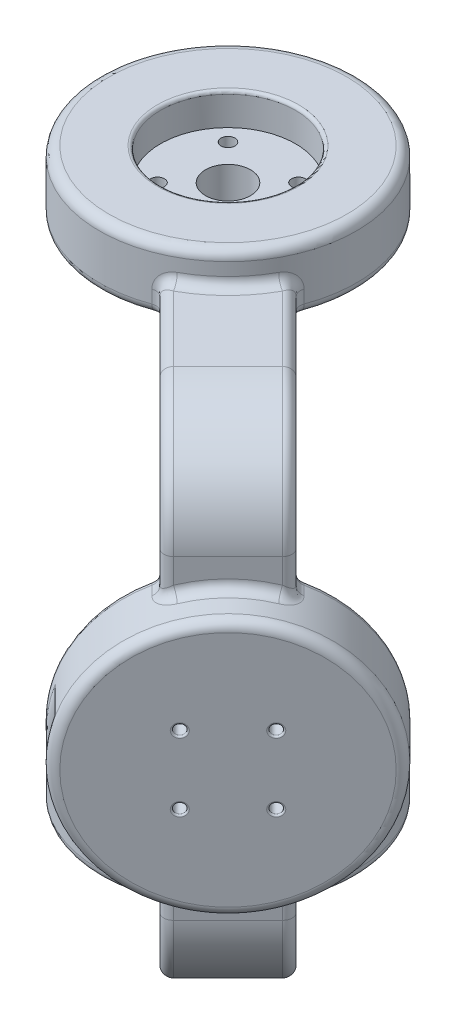
SolidWorks part; units mm, degrees
note: The reader was unsure of these and kept them because the rebuilt part matched: shared geometry of "草图6<4>".
ref_plane "前视基准面" through (0, 0, 0) normal (0, 0, 1) x (1, 0, 0)
ref_plane "上视基准面" through (0, 0, 0) normal (0, 1, 0) x (1, 0, 0)
ref_plane "右视基准面" through (0, 0, 0) normal (1, 0, 0) x (0, 0, -1)
other "Configuration Table"
sketch "草图2" plane through (0, 0, 0) normal (0, 0, 1) x (1, 0, 0)
  line L1 (30, -3) -> (30, -6)
  line L2 (30, -6) -> (40, -6)
  line L3 (40, -6) -> (40, 5)
  line L4 (25, 5) -> (0, 5)
  line L5 (0, 5) -> (0, 0)
  line L6 (0, 0) -> (25, 0)
  line L7 (25, 0) -> (25, -3)
  line L8 (25, -3) -> (30, -3)
  line L9 (40, 5) -> (40, 14)
  line L10 (40, 14) -> (25, 14)
  line L11 (25, 14) -> (25, 5)
revolve "旋转1" add sketch "草图2" angle 360 about L5
sketch "草图3" plane through (0, 0, 0) normal (0, -1, 0) x (1, 0, 0)
  circle A0 centre (12.5, 0) radius 1.6
  circle A1 centre (0, -12.5) radius 1.6
  circle A2 centre (-12.5, 0) radius 1.6
  circle A3 centre (0, 12.5) radius 1.6
  point P13 (0, 0)
  dimension "D1" = 4
extrude "切除-拉伸1" cut sketch "草图3" against normal blind 10
fillet "圆角3" radius 5 1 edges at (0, 14, 25)
sketch "草图5" plane through (0, 5, 0) normal (0, 1, 0) x (1, 0, 0)
  line L3 (0, 0) -> (6.25, -6.25)
ref_plane "基准面1" through (0, 0, 0) normal (-0.7071, 0, 0.7071) x (0.7071, 0, 0.7071)
sketch "草图6" plane through (0, 0, 0) normal (-0.7071, 0, 0.7071) x (0.7071, 0, 0.7071)
  line L0 (30, 14) -> (30, 4)
  line L1 (100, 53) -> (100, 83)
  line L5 (40, 14) -> (70, 14)
  line L8 (90, 34) -> (90, 53)
  line L13 (40, 14) -> (30, 14)
  line L17 (90, 53) -> (100, 53)
  line L18 (100, 53) -> (100, 34)
  line L19 (70, 4) -> (30, 4)
  line L27 (30, 152) -> (30, 162)
  line L28 (70, 162) -> (30, 162)
  line L29 (100, 113) -> (100, 132)
  line L30 (90, 113) -> (100, 113)
  line L31 (90, 132) -> (90, 113)
  line L32 (40, 152) -> (70, 152)
  line L33 (40, 152) -> (30, 152)
  arc A0 (90, 34) -> (70, 14) centre (70, 34) cw
  arc A2 (100, 34) -> (70, 4) centre (70, 34) cw
  arc A5 (100, 132) -> (70, 162) centre (70, 132) ccw
  arc A6 (90, 132) -> (70, 152) centre (70, 132) ccw
  dimension "D1" = 20
  dimension "D2" = 30
  dimension "D3" = 30
  dimension "D4" = 40
  dimension "D5" = 19
ref_plane "基准面2" through (0, 0, 0) normal (-0.7071, 0, 0.7071) x (0.7071, 0, 0.7071)
sketch "草图7" plane through (0, 0, 0) normal (-0.7071, 0, 0.7071) x (0.7071, 0, 0.7071)
  line L10 (90, 53) -> (103, 53)
  line L11 (103, 53) -> (103, 58)
  line L12 (103, 58) -> (107, 58)
  line L13 (107, 58) -> (107, 83)
  line L14 (107, 83) -> (112, 83)
  line L15 (112, 83) -> (112, 43)
  line L16 (90, 53) -> (90, 43)
  line L17 (112, 43) -> (90, 43)
revolve "旋转2" add sketch "草图7" angle 360 about L14
extrude "凸台-拉伸2" add sketch "草图6" along normal mid plane 30 contours L18 A2 L19 L0 L13 L5 A0 L8 L17
sketch "草图8" plane through (75.6604, 0, 75.6604) normal (-0.7071, 0, -0.7071) x (-0.7071, 0, 0.7071)
  circle A0 centre (10.6066, 93.6066) radius 1.6
  circle A1 centre (10.6066, 72.3934) radius 1.6
  circle A2 centre (-10.6066, 72.3934) radius 1.6
  circle A3 centre (-10.6066, 93.6066) radius 1.6
  point P13 (0, 83)
  dimension "D2" = 3.2
  dimension "D3" = 4
extrude "切除-拉伸3" cut sketch "草图8" against normal mid plane 30
fillet "圆角4" radius 0.5 4 edges at (-12.5, 5, -1.6) (12.5, 5, -1.6) (0, 5, -14.1) (0, 5, 10.9)
fillet "圆角5" radius 0.5 4 edges at (85.5646, 72.3934, 72.8273) (70.5646, 72.3934, 87.8273) (70.5646, 93.6066, 87.8273) (85.5646, 93.6066, 72.8273)
fillet "圆角7" radius 1 2 edges at (51.6188, 83, 94.0452) (55.1543, 83, 90.5097)
sketch "草图9" plane through (75.6604, 0, 75.6604) normal (-0.7071, 0, -0.7071) x (-0.7071, 0, 0.7071)
  line L0 (0, 83) -> (19.5212, 83)
ref_plane "基准面3" through (0, 83, 0) normal (0, -1, 0) x (-0.7071, 0, 0.7071)
fillet "圆角11" radius 3 1 edges at (0, -6, 40)
extrude "凸台-拉伸4" add sketch "草图6<4>" along normal mid plane 30 contours A5 L28 L27 L33 L32 A6 L31 L30 L29
sketch "草图6<4>" plane through (0, 0, 0) normal (-0.7071, 0, 0.7071) x (0.7071, 0, 0.7071) same geometry as "草图6"
mirror "镜向10" about plane through (0, 83, 0) normal (0, -1, 0) of "圆角11", "旋转1"
fillet "圆角12" radius 3 41 edges at (56.5685, 120.081, 77.7817) (70.7107, 123, 70.7107) (70.7107, 43, 70.7107) (-28.2843, 152, -28.2843) (70.1041, 146.1421, 48.8909) (53.8909, 153.2132, 75.1041) (60.1041, 126.0405, 81.3173) (27.2522, 162, 48.4654) (27.2522, 152, 48.4654) (48.8909, 146.1421, 70.1041) (48.4654, 152, 27.2522) (48.4654, 162, 27.2522) (75.1041, 153.2132, 53.8909) (81.3173, 126.0405, 60.1041) (77.7817, 120.081, 56.5685) (53.033, 126.0405, 74.2462) (74.2462, 126.0405, 53.033) (91.9239, 83, 35.3553) (35.3553, 83, 91.9239) (15.6136, 9, 36.8268) (28.2843, 4, 28.2843) (36.8268, 9, 15.6136) (-28.2843, 14, -28.2843) (77.7817, 45.919, 56.5685) (81.3173, 39.9595, 60.1041) (74.2462, 39.9595, 53.033) (70.1041, 19.8579, 48.8909) (75.1041, 12.7868, 53.8909) (48.4654, 14, 27.2522) (48.4654, 4, 27.2522) (27.2522, 14, 48.4654) (27.2522, 4, 48.4654) (53.8909, 12.7868, 75.1041) (60.1041, 39.9595, 81.3173) (56.5685, 45.919, 77.7817) (53.033, 39.9595, 74.2462) (48.8909, 19.8579, 70.1041) (28.2843, 162, 28.2843) (15.6136, 157, 36.8268) (36.8268, 157, 15.6136) (50.9117, 83, 107.4802)
sketch "草图10" plane through (0, 172, 0) normal (0, 1, 0) x (1, 0, 0)
  circle A0 centre (0, 0) radius 30
extrude "凸台-拉伸5" add sketch "草图10" against normal blind 20
sketch "草图11" plane through (0, 172, 0) normal (0, 1, 0) x (1, 0, 0)
  circle A0 centre (0, 0) radius 21
extrude "切除-拉伸4" cut sketch "草图11" against normal blind 10
sketch "草图12" plane through (0, 162, 0) normal (0, 1, 0) x (1, 0, 0)
  line L0 (0, 0) -> (10.9602, -10.9602)
  line L1 (-38.8909, 38.8909) -> (38.8909, -38.8909) construction
  circle A0 centre (10.9602, -10.9602) radius 2.15
  circle A1 centre (-10.9602, -10.9602) radius 2.15
  circle A2 centre (-10.9602, 10.9602) radius 2.15
  circle A3 centre (10.9602, 10.9602) radius 2.15
  point P15 (0, 0)
  dimension "D1" = 4
extrude "切除-拉伸5" cut sketch "草图12" against normal blind 10 contours A1 | A2 | A3 | A0
sketch "草图13" plane through (0, 162, 0) normal (0, 1, 0) x (1, 0, 0)
  circle A0 centre (0, 0) radius 7
extrude "切除-拉伸6" cut sketch "草图13" against normal blind 10
sketch "草图16" plane through (0, 0, 0) normal (-0.7071, 0, 0.7071) x (0.7071, 0, 0.7071)
  line L1 (-38.8909, 83) -> (38.8909, 83) construction
  line L2 (107, 83) -> (107, 73)
  line L3 (107, 73) -> (99, 73)
  line L4 (99, 73) -> (99, 93)
  line L5 (99, 93) -> (107, 93)
  line L6 (107, 93) -> (107, 83)
extrude "切除-拉伸7" cut sketch "草图16" along normal blind 62 contours L4 L5 L6 L2 L3
fillet "圆角13" radius 2 4 edges at (41.7193, 83, 98.2878) (47.3762, 83, 103.9447) (45.4459, 93, 100.2181) (45.4459, 73, 100.2181)
fillet "圆角14" radius 1 1 edges at (0, -3, 25)
fillet "圆角15" radius 1 1 edges at (0, 172, 21)
